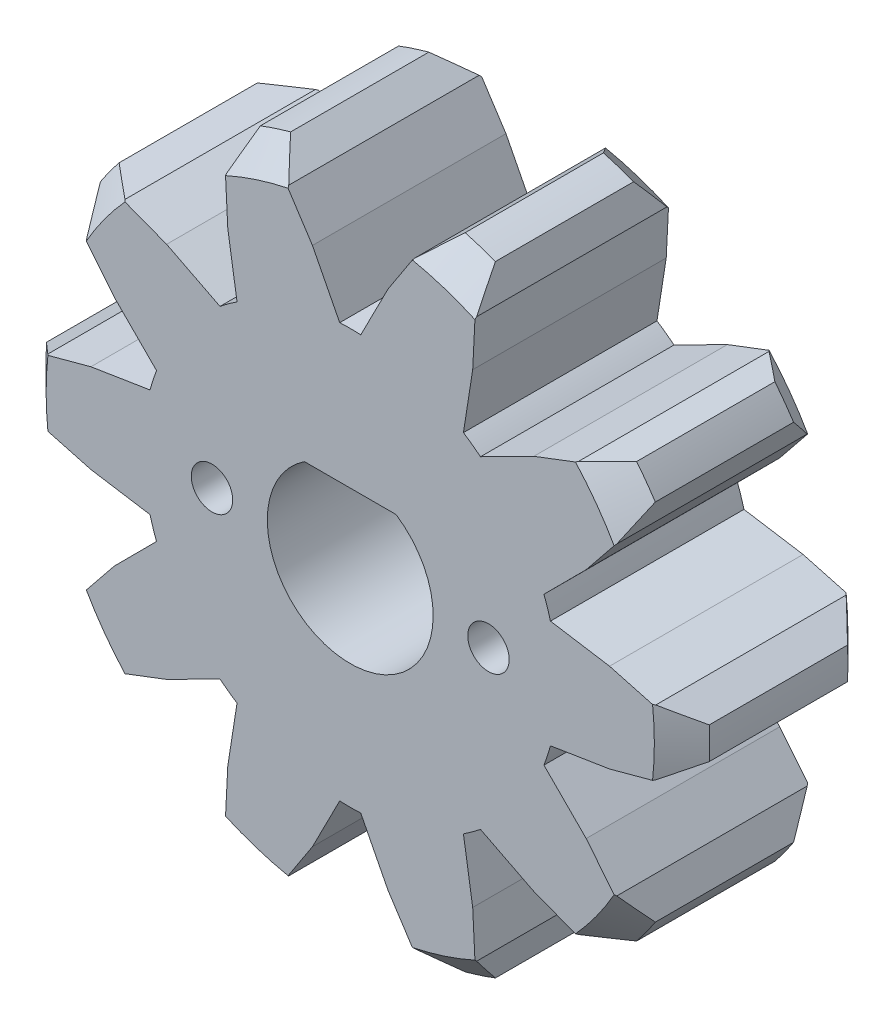
SolidWorks part; units mm, degrees
ref_plane "前视基准面" through (0, 0, 0) normal (0, 0, 1) x (1, 0, 0)
ref_plane "上视基准面" through (0, 0, 0) normal (0, 1, 0) x (1, 0, 0)
ref_plane "右视基准面" through (0, 0, 0) normal (1, 0, 0) x (0, 0, -1)
sketch "草图1" plane through (0, 0, 0) normal (0, 0, 1) x (1, 0, 0)
  circle A0 centre (0, 0) radius 12
extrude "凸台-拉伸1" add sketch "草图1" along normal blind 7
ref_axis "基准轴1" through (0, 0, -1.5) along (0, 0, 1)
chamfer "倒角1" distance 1 angle 45 2 edges at (12, 0, 0) (12, 0, 7)
sketch "草图2" plane through (0, 0, 0) normal (0, 0, 1) x (1, 0, 0)
  line L0 (0, 0) -> (0, 12) construction
  line L1 (-0.3809, 7.4903) -> (-1.3672, 9.4177)
  line L2 (-1.3672, 9.4177) -> (-2.2813, 10.8186)
  line L3 (-2.2813, 10.8186) -> (-3.1875, 11.6041)
  line L4 (-3.1875, 11.6041) -> (-3.2551, 11.6626)
  line L5 (3.1875, 11.6041) -> (3.2551, 11.6626)
  line L6 (0.3809, 7.4903) -> (1.3672, 9.4177)
  line L7 (1.3672, 9.4177) -> (2.2813, 10.8186)
  line L8 (2.2813, 10.8186) -> (3.1875, 11.6041)
  circle A0 centre (0, 0) radius 12 construction
  arc A1 (0.3809, 7.4903) -> (-0.3809, 7.4903) centre (0, 0) ccw
extrude "切除-拉伸1" cut sketch "草图2" along normal through all
pattern_circular "阵列(圆周)1" count 10 every 36 about axis through (0, 0, -1.5) along (0, 0, 1) of "切除-拉伸1"
sketch "草图3" plane through (0, 0, 0) normal (0, 0, 1) x (1, 0, 0)
  circle A0 centre (0, 0) radius 10 construction
  dimension "Dn" = 20
sketch "草图4" plane through (0, 0, 0) normal (0, 0, 1) x (1, 0, 0)
  line L0 (-0.9, 2.5) -> (0.9, 2.5)
  line L3 (-0.9, 2.5) -> (-1.6583, 2.5)
  line L4 (0.9, 2.5) -> (1.6583, 2.5)
  arc A0 (-1.6583, 2.5) -> (1.6583, 2.5) centre (0, 0) ccw
  circle A1 centre (5, 0) radius 0.75
  circle A2 centre (-5, 0) radius 0.75
  dimension "D1" = 3
  dimension "D3" = 5
  dimension "D2" = 2.5
  dimension "D4" = 5
extrude "切除-拉伸2" cut sketch "草图4" along normal through all
